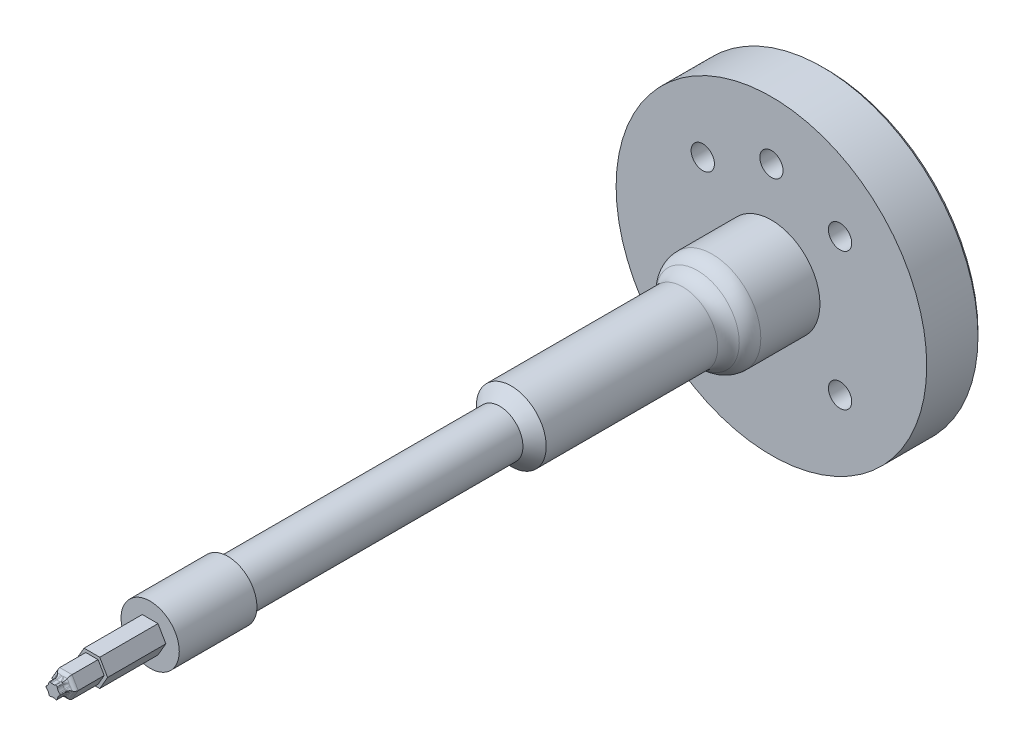
SolidWorks part; units mm, degrees
material "6061-T6 (SS)"
ref_plane "Ebene vorne" through (0, 0, 0) normal (0, 0, 1) x (1, 0, 0)
ref_plane "Ebene oben" through (0, 0, 0) normal (0, 1, 0) x (1, 0, 0)
ref_plane "Ebene rechts" through (0, 0, 0) normal (1, 0, 0) x (0, 0, -1)
sketch "Skizze1" plane through (0, 0, 0) normal (0, 0, 1) x (1, 0, 0)
  circle A0 centre (0, 0) radius 40
  circle A1 centre (0, 0) radius 31.5
  dimension "D1" = 80
  dimension "D2" = 63
extrude "Aufsatz-Linear austragen1" add sketch "Skizze1" along normal blind 6.2
sketch "Skizze2" plane through (0, 0, 6.2) normal (0, 0, 1) x (1, 0, 0)
  circle A0 centre (0, 0) radius 40
extrude "Aufsatz-Linear austragen2" add sketch "Skizze2" along normal blind 8
sketch "Skizze3" plane through (0, 0, 6.2) normal (0, 0, -1) x (-1, 0, 0)
  circle A0 centre (0, 0) radius 15.75
  circle A1 centre (0, 25) radius 3
  circle A2 centre (17.6777, 17.6777) radius 3
  circle A3 centre (17.6777, -17.6777) radius 3
  circle A4 centre (-17.6777, -17.6777) radius 3
  circle A5 centre (-17.6777, 17.6777) radius 3
  point P9 (0, 0)
  point P17 (0, 0)
  dimension "D1" = 31.5
  dimension "D2" = 6
  dimension "D3" = 25
  dimension "D4" = 2
  dimension "D5" = 4
extrude "Schnitt-Linear austragen1" cut sketch "Skizze3" against normal blind 8 contours A4 | A5 | A1 | A2 | A3 region at (0, 25, 6.2) region at (-17.6777, 17.6777, 6.2) region at (17.6777, -17.6777, 6.2) region at (17.6777, 17.6777, 6.2)
shell "Wandung1" thickness 3
chamfer "Fase1" distance 1 angle 45 1 edges at (40, 0, 0)
sketch "Skizze4" plane through (0, 0, 14.2) normal (0, 0, 1) x (1, 0, 0)
  circle A0 centre (0, 0) radius 12.5
  dimension "D1" = 25
extrude "Aufsatz-Linear austragen3" add sketch "Skizze4" along normal blind 20
chamfer "Fase2" distance 1 angle 45 5 edges at (14.6777, -17.6777, 6.2) (-20.6777, -17.6777, 6.2) (-20.6777, 17.6777, 6.2) (-3, 25, 6.2) (14.6777, 17.6777, 6.2)
sketch "Skizze5" plane through (0, 0, 34.2) normal (0, 0, 1) x (1, 0, 0)
  circle A0 centre (0, 0) radius 9
  dimension "D1" = 18
extrude "Aufsatz-Linear austragen4" add sketch "Skizze5" along normal blind 50
fillet "Verrundung1" radius 5 1 edges at (12.5, 0, 34.2)
fillet "Verrundung2" radius 5 1 edges at (9, 0, 34.2)
sketch "Skizze6" plane through (0, 0, 84.2) normal (0, 0, 1) x (1, 0, 0)
  circle A0 centre (0, 0) radius 6
  dimension "D1" = 12
extrude "Aufsatz-Linear austragen5" add sketch "Skizze6" along normal blind 70
chamfer "Fase3" distance 3 angle 45 1 edges at (9, 0, 84.2)
sketch "Skizze7" plane through (0, 0, 154.2) normal (0, 0, 1) x (1, 0, 0)
  circle A0 centre (0, 0) radius 7.5
  dimension "D1" = 15
extrude "Aufsatz-Linear austragen6" add sketch "Skizze7" along normal blind 20
sketch "Skizze8" plane through (0, 0, 174.2) normal (0, 0, 1) x (1, 0, 0)
  line L1 (3.175, 0) -> (1.5875, 2.7496)
  line L2 (1.5875, 2.7496) -> (-1.5875, 2.7496)
  line L3 (-1.5875, 2.7496) -> (-3.175, 0)
  line L4 (-3.175, 0) -> (-1.5875, -2.7496)
  line L5 (-1.5875, -2.7496) -> (1.5875, -2.7496)
  line L6 (1.5875, -2.7496) -> (3.175, 0)
  circle A0 centre (0, 0) radius 2.7496 construction
  dimension "D1" = 6.35
extrude "Aufsatz-Linear austragen7" add sketch "Skizze8" along normal blind 22.7
sketch "Skizze9" plane through (0, 0, 196.9) normal (0, 0, 1) x (1, 0, 0)
  line L0 (-1.2124, 0.7) -> (-0.98, 1.6974)
  line L7 (0, 1.4) -> (-0.98, 1.6974)
  line L8 (0, 1.4) -> (0.98, 1.6974)
  line L9 (0.98, 1.6974) -> (1.2124, 0.7)
  line L10 (1.2124, 0.7) -> (1.96, 0)
  line L11 (1.96, 0) -> (1.2124, -0.7)
  line L12 (1.2124, -0.7) -> (0.98, -1.6974)
  line L13 (-0.98, -1.6974) -> (0, -1.4)
  line L14 (0, -1.4) -> (0.98, -1.6974)
  line L15 (-0.98, -1.6974) -> (-1.2124, -0.7)
  line L16 (-1.2124, -0.7) -> (-1.96, 0)
  line L17 (-1.2124, 0.7) -> (-1.96, 0)
  point P1 (0, 1.4)
  point P14 (1.2124, 0.7)
  point P15 (1.2124, -0.7)
  point P16 (0, -1.4)
  point P17 (-1.2124, -0.7)
  point P18 (-1.2124, 0.7)
  dimension "D1" = 3.92
  dimension "D3" = 6
extrude "Aufsatz-Linear austragen8" add sketch "Skizze9" along normal blind 2.3
fillet "Verrundung4" radius 1.5 6 edges at (1.2124, -0.7, 198.05) (1.2124, 0.7, 198.05) (0, -1.4, 198.05) (-1.2124, -0.7, 198.05) (-1.2124, 0.7, 198.05) (0, 1.4, 198.05)
fillet "Verrundung5" radius 0.3 6 edges at (0.98, 1.6974, 198.05) (1.96, 0, 198.05) (0.98, -1.6974, 198.05) (-0.98, -1.6974, 198.05) (-0.98, 1.6974, 198.05) (-1.96, 0, 198.05)
chamfer "Fase7" distance 1 angle 45 1 edges at (6, 0, 154.2)
sketch "Skizze10" plane through (0, 0, 174.2) normal (0, 0, 1) x (1, 0, 0)
  line L1 (1.5875, 2.7496) -> (-1.5875, 2.7496)
  line L2 (-1.5875, 2.7496) -> (-3.175, 0)
  line L3 (-3.175, 0) -> (-1.5875, -2.7496)
  line L4 (-1.5875, -2.7496) -> (1.5875, -2.7496)
  line L5 (1.5875, -2.7496) -> (3.175, 0)
  line L6 (3.175, 0) -> (1.5875, 2.7496)
  line L7 (2.0207, 3.5) -> (-2.0207, 3.5)
  line L8 (-2.0207, 3.5) -> (-4.0415, 0)
  line L9 (-4.0415, 0) -> (-2.0207, -3.5)
  line L10 (-2.0207, -3.5) -> (2.0207, -3.5)
  line L11 (2.0207, -3.5) -> (4.0415, 0)
  line L12 (4.0415, 0) -> (2.0207, 3.5)
  circle A0 centre (0, 0) radius 2.7496 construction
  circle A1 centre (0, 0) radius 3.5 construction
extrude "Aufsatz-Linear austragen9" add sketch "Skizze10" along normal blind 15
fillet "Verrundung8" radius 1 6 edges at (0, 2.7496, 196.9) (2.3812, 1.3748, 196.9) (2.3812, -1.3748, 196.9) (0, -2.7496, 196.9) (-2.3813, -1.3748, 196.9) (-2.3813, 1.3748, 196.9)
fillet "Verrundung9" radius 1 18 edges at (-1.0809, -1.2644, 196.9) (-0.5545, -1.5683, 196.9) (0, -1.4676, 196.9) (0.5545, -1.5683, 196.9) (1.0809, -1.2644, 196.9) (1.2709, -0.7338, 196.9) (1.6354, -0.3039, 196.9) (1.6354, 0.3039, 196.9) (1.2709, 0.7338, 196.9) (1.0809, 1.2644, 196.9) (0.5545, 1.5683, 196.9) (0, 1.4676, 196.9) (-0.5545, 1.5683, 196.9) (-1.0809, 1.2644, 196.9) (-1.2709, 0.7338, 196.9) (-1.6354, 0.3039, 196.9) (-1.6354, -0.3039, 196.9) (-1.2709, -0.7338, 196.9)
